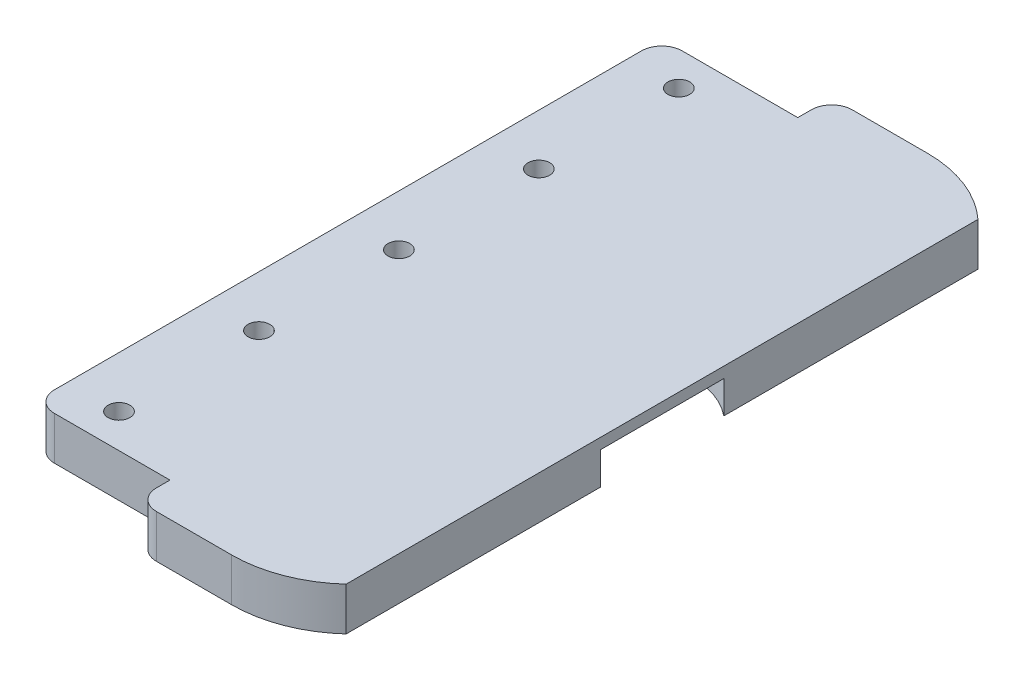
SolidWorks part; units mm, degrees
ref_plane "Front Plane" through (0, 0, 0) normal (0, 0, 1) x (1, 0, 0)
ref_plane "Top Plane" through (0, 0, 0) normal (0, 1, 0) x (1, 0, 0)
ref_plane "Right Plane" through (0, 0, 0) normal (1, 0, 0) x (0, 0, -1)
sketch "Sketch1" plane through (0, 0, 0) normal (0, 1, 0) x (1, 0, 0)
  line L0 (7.5, 102.362) -> (7.5, 0) construction
  line L1 (0, 0) -> (52.084, 0)
  line L2 (0, 0) -> (0, 102.362)
  line L3 (0, 102.362) -> (52.084, 102.362)
  line L4 (52.084, 0) -> (52.084, 102.362)
  line L5 (30.3604, 43.18) -> (30.3604, 59.18)
  line L6 (20, 0) -> (0, 0)
  line L7 (20, 0) -> (20, 5)
  line L8 (20, 5) -> (0, 5)
  line L9 (0, 0) -> (0, 5)
  line L10 (0, 102.362) -> (20, 102.362)
  line L11 (0, 102.362) -> (0, 97.362)
  line L12 (0, 97.362) -> (20, 97.362)
  line L13 (20, 102.362) -> (20, 97.362)
  circle A0 centre (38.876, 95.63) radius 3.45
  arc A1 (30.3604, 43.18) -> (30.3604, 59.18) centre (38.876, 51.18) ccw
  circle A2 centre (38.876, 6.73) radius 3.45
  circle A3 centre (7.5, 92.362) radius 1.6
  circle A4 centre (7.5, 71.772) radius 1.6
  circle A5 centre (7.5, 51.182) radius 1.6
  circle A6 centre (7.5, 30.592) radius 1.6
  circle A7 centre (7.5, 10.002) radius 1.6
  dimension "D4" = 6.9
  dimension "D5" = 23.368
  dimension "D11" = 3.2
  dimension "D1" = 102.362
  dimension "D2" = 52.084
  dimension "D6" = 44.45
  dimension "D7" = 44.45
  dimension "D8" = 51.18
  dimension "D9" = 13.208
  dimension "D10" = 7.5
  dimension "D12" = 10
  dimension "D14" = 20
  dimension "D15" = 5
  dimension "D18" = 20.59
  dimension "D19" = 16
  dimension "D13" = 5
extrude "Boss-Extrude1" add sketch "Sketch1" along normal blind 6.35 contours L1 L4 L3 L2
extrude "Cut-Extrude2" cut sketch "Sketch1<4>" along normal through all contours A4 L0 | L0 A4 | A3 | A5 | A6 | A7 region at (8.1791, 0, -71.772) region at (6.8209, 0, -71.772)
sketch "Sketch1<4>" plane through (0, 0, 0) normal (0, 1, 0) x (1, 0, 0) same geometry as "Sketch1"
extrude "Cut-Extrude3" cut sketch "Sketch1<5>" along normal offset from surface (4.7625 mm away) 1.5875 contours A1 | A0 | A2 region at (39.7422, 0, -51.18) region at (38.876, 0, -95.63) up to face at (7.5, 6.35, -8.402)
sketch "Sketch1<5>" plane through (0, 0, 0) normal (0, 1, 0) x (1, 0, 0) same geometry as "Sketch1"
fillet "Fillet1" radius 18 2 edges at (52.084, 3.175, -102.362) (52.084, 3.175, 0)
extrude "Cut-Extrude4" cut sketch "Sketch1<7>" along normal through all contours L6 L7 L8 L9 | L10 L13 L12 L11
sketch "Sketch1<7>" plane through (0, 0, 0) normal (0, 1, 0) x (1, 0, 0) same geometry as "Sketch1"
fillet "Fillet4" radius 3 4 edges at (20, 3.175, -102.362) (0, 3.175, -97.362) (0, 3.175, -5) (20, 3.175, 0)
sketch "Sketch3" plane through (0, 0, 0) normal (0, -1, 0) x (1, 0, 0)
  line L1 (46.2193, -4.7058) -> (68.6711, -4.7058)
  line L2 (46.2193, -4.7058) -> (46.2193, -97.6562)
  line L3 (46.2193, -97.6562) -> (68.6711, -97.6562)
  line L4 (68.6711, -4.7058) -> (68.6711, -97.6562)
  arc A0 (52.084, -18) -> (34.084, 0) centre (34.084, -18) ccw construction
  arc A1 (34.084, -102.362) -> (52.084, -84.362) centre (34.084, -84.362) ccw construction
extrude "Cut-Extrude6" cut sketch "Sketch3" against normal blind 6.35
